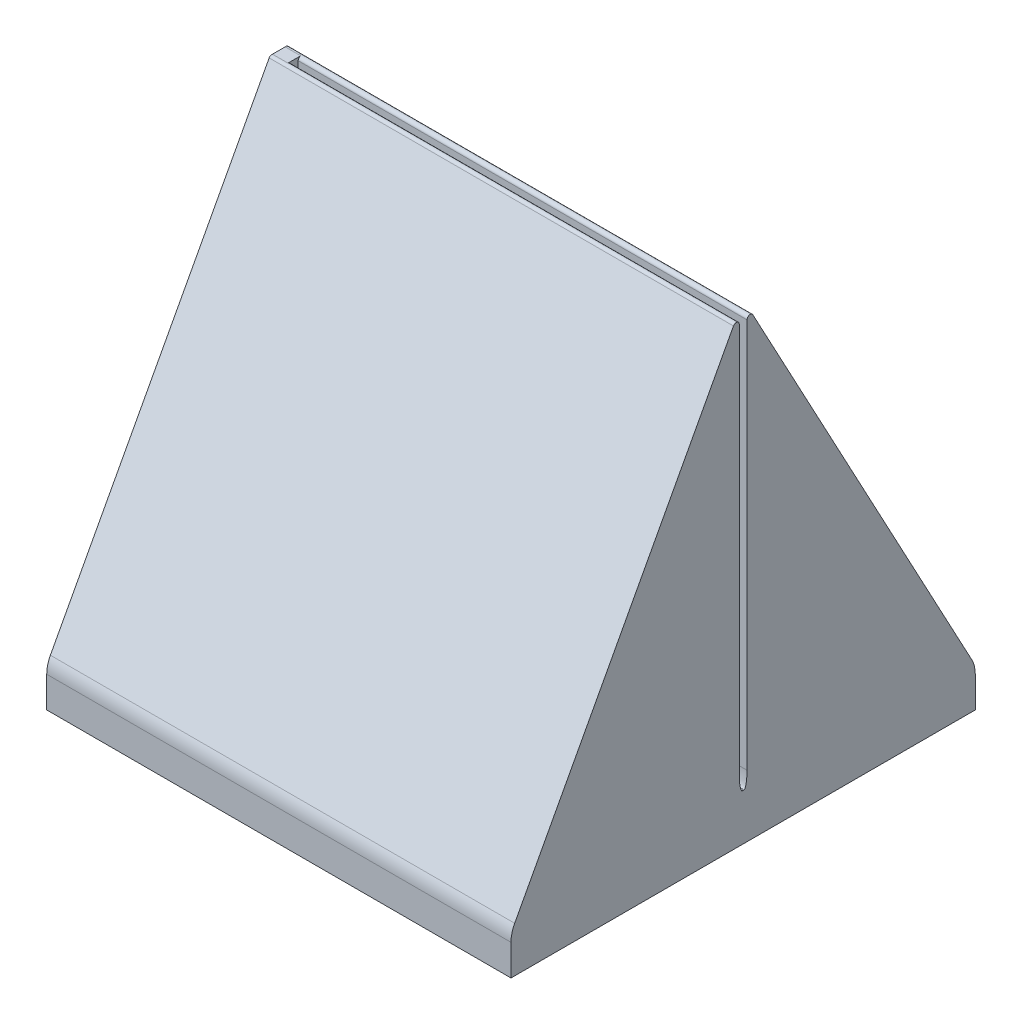
SolidWorks part; units mm, degrees
ref_plane "Front Plane" through (0, 0, 0) normal (0, 0, 1) x (1, 0, 0)
ref_plane "Top Plane" through (0, 0, 0) normal (0, 1, 0) x (1, 0, 0)
ref_plane "Right Plane" through (0, 0, 0) normal (1, 0, 0) x (0, 0, -1)
sketch "Sketch1" plane through (0, 0, 0) normal (1, 0, 0) x (0, 0, -1)
  line L0 (0, 0) -> (76.2, 0)
  line L1 (76.2, 0) -> (76.2, 6.35)
  line L2 (76.2, 6.35) -> (38.735, 76.2)
  line L5 (37.465, 76.2) -> (0, 6.35)
  line L6 (0, 6.35) -> (0, 0)
  line L7 (37.465, 76.2) -> (37.465, 7.62)
  line L8 (37.465, 7.62) -> (38.735, 7.62)
  line L9 (38.735, 7.62) -> (38.735, 76.2)
  dimension "D1" = 7.62
  dimension "D2" = 76.2
  dimension "D3" = 6.35
  dimension "D4" = 76.2
  dimension "D6" = 1.27
extrude "Boss-Extrude1" add sketch "Sketch1" along normal blind 76.2
sketch "Sketch2" plane through (0, 0, 0) normal (-1, 0, 0) x (0, 0, 1)
  line L0 (-37.465, 7.62) -> (-37.465, 76.2) construction
  line L1 (-38.735, 7.62) -> (-37.465, 7.62)
  line L2 (-38.735, 7.62) -> (-38.735, 74.676)
  line L3 (-38.735, 74.676) -> (-37.465, 74.676)
  line L4 (-37.465, 7.62) -> (-37.465, 74.676)
  point P6 (-37.465, 74.6854)
  dimension "D1" = 1.524
extrude "Boss-Extrude2" add sketch "Sketch2" against normal blind 2.54
fillet "Fillet1" radius 5.08 2 edges at (38.1, 6.35, -76.2) (38.1, 6.35, 0)
fillet "Fillet2" radius 0.508 2 edges at (39.37, 7.62, -38.735) (39.37, 7.62, -37.465) second distance 2.54 first distance on face at (39.37, 7.62, -38.1)
fillet "Fillet3" radius 0.508 2 edges at (38.1, 76.2, -38.735) (38.1, 76.2, -37.465) tangent propagation no
